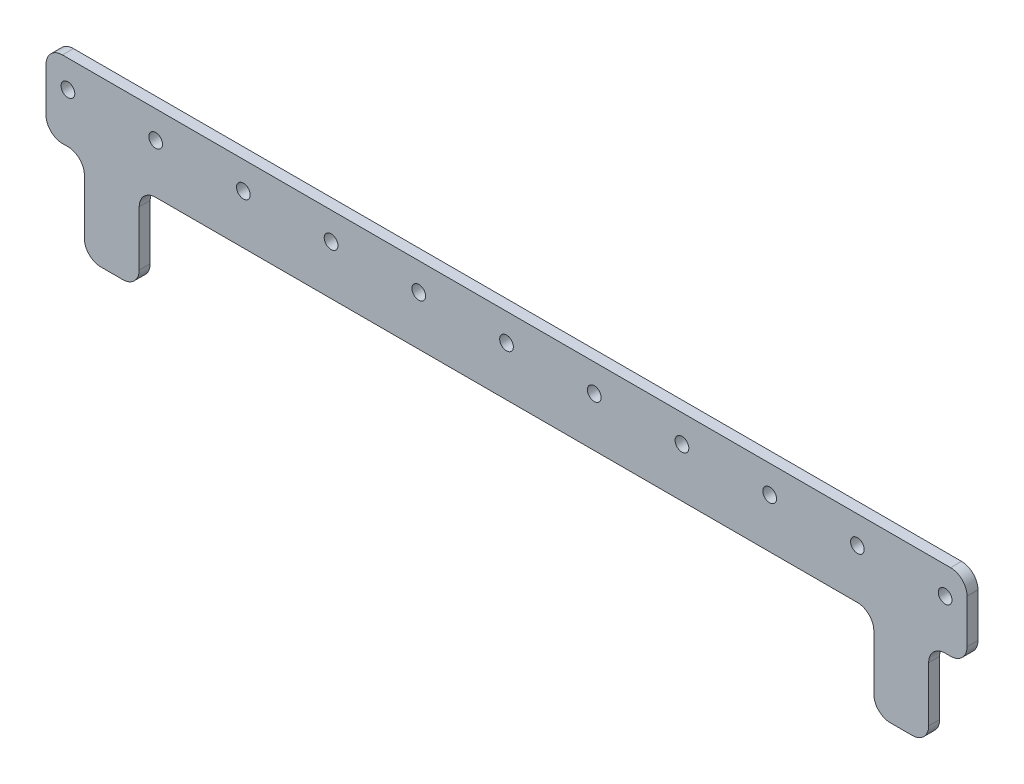
SolidWorks part; units mm, degrees
ref_plane "Top" through (0, 0, 0) normal (0, 0, 1) x (1, 0, 0)
ref_plane "Front" through (0, 0, 0) normal (0, 1, 0) x (1, 0, 0)
ref_plane "Right" through (0, 0, 0) normal (1, 0, 0) x (0, 0, -1)
sketch "Base Sketch" plane through (0, 0, 0) normal (0, 0, 1) x (1, 0, 0)
  line L0 (-84, 7) -> (84, -7) construction
  line L1 (-84, 7) -> (84, 7)
  line L2 (-84, 7) -> (-84, -7)
  line L3 (-84, -7) -> (84, -7)
  line L4 (84, 7) -> (84, -7)
  point P4 (0, 0)
  dimension "Length" = 168
  dimension "D2" = 14
extrude "Base Extrude" add sketch "Base Sketch" against normal blind 2
sketch "Handle Sketch" [suppressed] plane through (68, 0, 0) normal (1, 0, 0) x (0, 0, -1)
  line L0 (0, -7) -> (-5, -3)
  line L1 (-5, -3) -> (-10, -3)
  line L2 (-10, -3) -> (-11.4004, -5)
  line L3 (-11.4004, -5) -> (-15, -5)
  line L4 (-15, -5) -> (-15, 0)
  line L5 (-15, 0) -> (0, 0)
  line L6 (0, -7) -> (0, 7) construction
  line L7 (0, 0) -> (0, -7)
  line L8 (-10, -3) -> (-10, 0) construction
  dimension "D1" = 5
  dimension "D2" = 3
  dimension "D3" = 5
  dimension "D4" = 15
  dimension "D5" = 5
  dimension "D6" = 35
extrude "Handle Extrude" [suppressed] add sketch "Handle Sketch" against normal through all
fillet "Handle Top Fillets" [suppressed] radius 1
fillet "Handle Side Fillet" [suppressed] radius 5
mirror "Handle Mirror" [suppressed]
sketch "Pin Hole Sketch" plane through (0, 0, 0) normal (0, 0, 1) x (1, 0, 0)
  circle A0 centre (80, 2) radius 1.25
  dimension "Diameter" = 2.5
  dimension "D1" = 4
  dimension "D2" = 5
extrude "First Pin Hole Cut" cut sketch "Pin Hole Sketch" against normal through all and the other way blind 5
pattern_linear "Pin Hole Pattern" count 11 spacing 16 along (-1, 0, 0) of "First Pin Hole Cut"
sketch "Extension Sketch" plane through (0, 0, 0) normal (0, 0, 1) x (1, 0, 0)
  line L0 (64, 2) -> (80, 2) construction
  line L1 (72, 2) -> (72, -23) construction
  line L2 (67, -23) -> (77, -23)
  line L3 (77, -23) -> (77, 2)
  line L4 (77, 2) -> (67, 2)
  line L5 (67, 2) -> (67, -23)
  circle A2 centre (80, 2) radius 1.25 construction
  circle A3 centre (64, 2) radius 1.25 construction
  dimension "D1" = 10
  dimension "D2" = 30
extrude "Tab Extrude" add sketch "Extension Sketch" against normal through all separate body
mirror "Tab Mirror" about plane through (0, 0, 0) normal (1, 0, 0) of "Tab Extrude"
combine bodies "Combine Bodies" operation type add bodies to combine 106 105
fillet "Corner Fillets" radius 3 12 edges at (84, 7, -1) (84, -7, -1) (-84, -7, -1) (-84, 7, -1) (67, -7, -1) (-77, -7, -1) (-67, -7, -1) (77, -7, -1) (-77, -23, -1) (-67, -23, -1) (67, -23, -1) (77, -23, -1)
